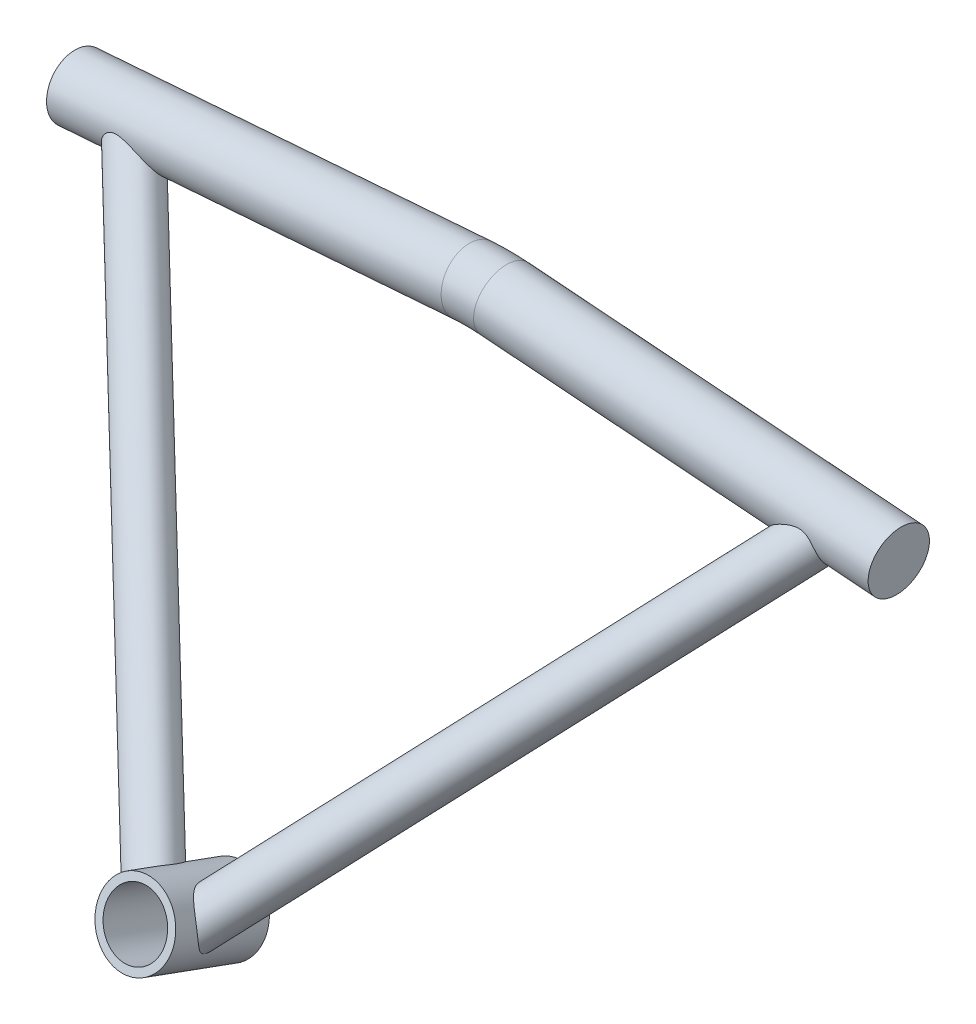
SolidWorks part; units mm, degrees
material "AISI 4130 Steel, normalized at 870C"
ref_plane "Front Plane" through (0, 0, 0) normal (0, 0, 1) x (1, 0, 0)
ref_plane "Top Plane" through (0, 0, 0) normal (0, 1, 0) x (1, 0, 0)
ref_plane "Right Plane" through (0, 0, 0) normal (1, 0, 0) x (0, 0, -1)
sketch "Sketch3" plane through (0, 0, 0) normal (0, 1, 0) x (1, 0, 0)
  line L0 (-5.08, -6.35) -> (5.08, -6.35) construction
  line L2 (0, -88.2205) -> (0, 88.2205) construction
  line L3 (5.08, 0) -> (-5.08, 0) construction
  dimension "D1" = 5.08
  dimension "D2" = 10.16
  dimension "D3" = 6.35
  dimension "D4" = 10.16
  dimension "D5" = 5.08
ref_plane "Plane1" through (0, 3.1441, 3.6169) normal (0, 0.6561, 0.7547) x (1, 0, 0)
ref_plane "Plane3" through (0, 0, 0) normal (0, 0.342, 0.9397) x (-1, 0, 0)
sketch "Sketch1" plane through (0, 0, 0) normal (0, 0.342, 0.9397) x (1, 0, 0)
  circle A0 centre (0, 0) radius 15.875
  dimension "D1" = 31.75
extrude "Boss-Extrude1" add sketch "Sketch1" along normal mid plane 41.402 contours A0
sketch "Sketch4" plane through (0, 3.1441, 3.6169) normal (0, 0.6561, 0.7547) x (1, 0, 0)
  line L0 (-5.08, -4.166) -> (-143.484, 193.4954)
  line L2 (0, -90.5202) -> (0, 90.5202) construction
  dimension "D2" = 35
  dimension "D3" = 241.3
sweep "Sweep1" add path "Sketch4" circular profile diameter 19.05 parameters "D3"=19.05
sketch "Sketch15" plane through (0, 3.1441, 3.6169) normal (0, 0.6561, 0.7547) x (1, 0, 0)
  line L0 (5.08, -4.166) -> (143.484, 193.4954)
  line L1 (0, -90.5202) -> (0, 90.5202) construction
  dimension "D1" = 241.3
  dimension "D2" = 35
sweep "Sweep2" add path "Sketch15" circular profile diameter 19.05 parameters "D3"=19.05
sketch "Sketch36" plane through (-138.1179, 148.8686, -129.4095) normal (-0.5736, 0.6182, -0.5374) x (0.8191, 0.4394, -0.3687)
  circle A0 centre (-6.5024, -4.8578) radius 7.9375
  dimension "D1" = 15.875
extrude "Cut-Extrude2" cut sketch "Sketch36" against normal up to surface (251.5099 mm away) up to face at (15.2328, -2.8486, 5.2417)
sketch "Sketch37" plane through (138.1179, 148.8686, -129.4095) normal (0.5736, 0.6182, -0.5374) x (0.8191, -0.4394, 0.3687)
  circle A0 centre (6.5024, -4.8578) radius 7.9375
  dimension "D1" = 15.875
extrude "Cut-Extrude3" cut sketch "Sketch37" against normal up to surface (226.8376 mm away) up to face at (10.6472, -5.7729, 18.5671)
sketch "Sketch77" plane through (0, 7.0802, 19.4526) normal (0, 0.342, 0.9397) x (1, 0, 0)
  circle A1 centre (0, 0) radius 15.875
extrude "Boss-Extrude2" add sketch "Sketch77" against normal up to surface (41.402 mm away) up to face at (0, -21.9978, -14.023)
sketch "Sketch2" plane through (0, -7.0802, -19.4526) normal (0, -0.342, -0.9397) x (-1, 0, 0)
  circle A0 centre (0, 0) radius 12.7
  dimension "D1" = 25.4
extrude "Cut-Extrude1" cut sketch "Sketch2" against normal up to next
ref_plane "Plane2" through (0, 0, -127) normal (0, 0, 1) x (1, 0, 0)
sketch "Sketch40" plane through (-106.934, 0, -127) normal (0, 0, 1) x (1, 0, 0)
  line L2 (106.934, -85.9333) -> (106.934, 85.9333) construction
  line L3 (100.2024, 162.3048) -> (-63.6638, 149.8608)
  line L4 (113.6656, 162.3048) -> (277.5318, 149.8608)
  arc A0 (100.2024, 162.3048) -> (113.6656, 162.3048) centre (106.934, 73.66) cw
  point P0 (106.934, 162.56)
  point P4 (0, 0)
  point P7 (106.934, 162.56)
  point P9 (0, 0)
  point P12 (0, 0)
  point P13 (0, 0)
  point P14 (0, 0)
  point P15 (0, 0)
  dimension "D1" = 164.338
  dimension "D3" = 88.9
  dimension "D2" = 164.338
  dimension "D4" = 4.75
sweep "Sweep3" add path "Sketch40" circular profile diameter 25.4 parameters "D3"=25.4
